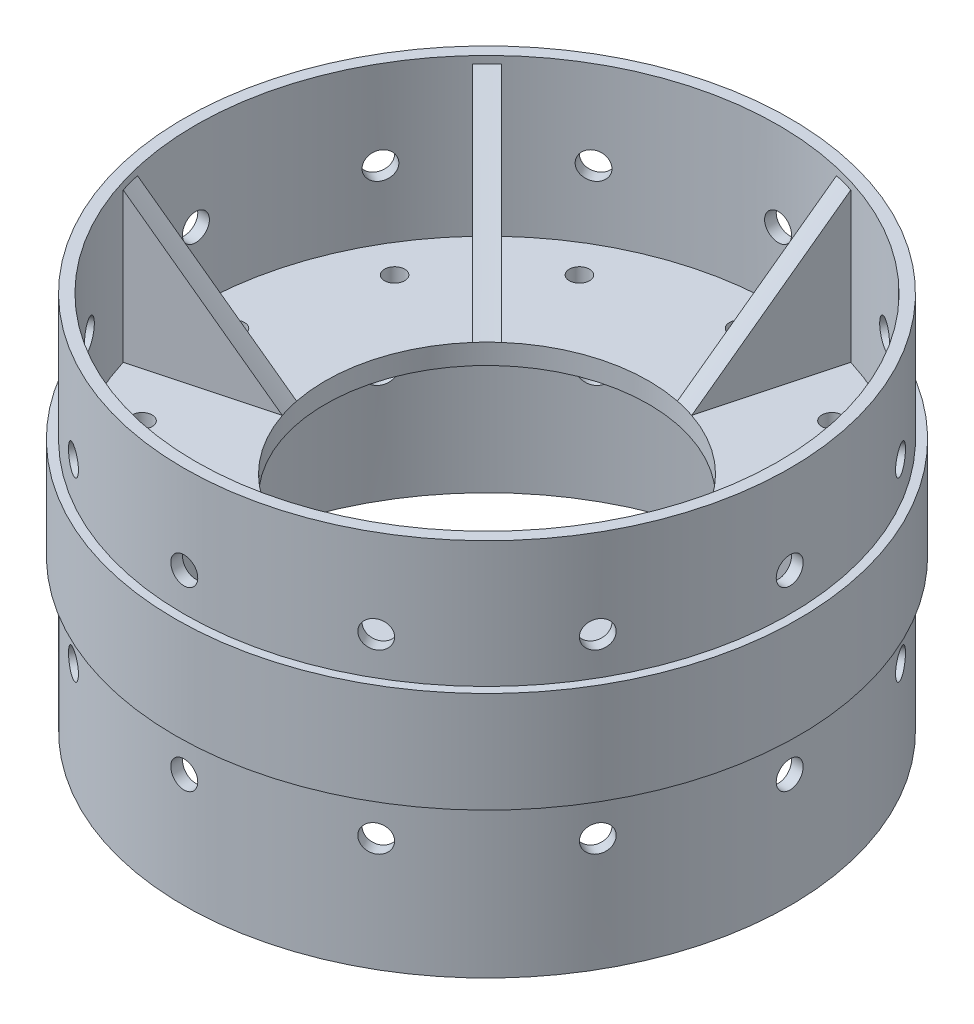
SolidWorks part; units mm, degrees
material "Onyx"
ref_plane "Front Plane" through (0, 0, 0) normal (0, 0, 1) x (1, 0, 0)
ref_plane "Top Plane" through (0, 0, 0) normal (0, 1, 0) x (1, 0, 0)
ref_plane "Right Plane" through (0, 0, 0) normal (1, 0, 0) x (0, 0, -1)
sketch "Sketch1" plane through (0, 0, 0) normal (0, 1, 0) x (1, 0, 0)
  circle A0 centre (0, 0) radius 73.279
  circle A1 centre (0, 0) radius 78.359
  dimension "D1" = 146.558
  dimension "D2" = 156.718
extrude "Boss-Extrude1" add sketch "Sketch1" along normal blind 25.4
sketch "Sketch2" plane through (0, 25.4, 0) normal (0, 1, 0) x (1, 0, 0)
  circle A0 centre (0, 0) radius 76.2
  circle A1 centre (0, 0) radius 73.279
  circle A2 centre (0, 0) radius 73.279 construction
  dimension "D1" = 0
extrude "Boss-Extrude2" add sketch "Sketch2" along normal blind 31.75
sketch "Sketch3" plane through (0, 0, 0) normal (0, -1, 0) x (1, 0, 0)
  circle A0 centre (0, 0) radius 76.2
  circle A1 centre (0, 0) radius 73.279
  circle A2 centre (0, 0) radius 73.279 construction
  dimension "D1" = 152.4
  dimension "D2" = 0
extrude "Boss-Extrude3" add sketch "Sketch3" along normal blind 38.1
ref_plane "Plane1" through (0, 12.7, 0) normal (0, 1, 0) x (1, 0, 0)
sketch "Sketch4" plane through (0, 12.7, 0) normal (0, 1, 0) x (1, 0, 0)
  circle A0 centre (0, 0) radius 74.549
  circle A1 centre (0, 0) radius 40.64
  dimension "D1" = 81.28
extrude "Boss-Extrude4" add sketch "Sketch4" along normal blind 5.08
sketch "Sketch5" plane through (0, 17.78, 0) normal (0, 1, 0) x (1, 0, 0)
  line L3 (0, 0) -> (40.64, 0) construction
  line L35 (38.5211, 12.9513) -> (70.0821, 21.4081)
  line L36 (39.8359, 8.0444) -> (71.3969, 16.5012)
  line L37 (70.7821, 18.966) -> (0, 0) construction
  line L38 (26.8846, -30.4767) -> (49.9889, -53.581)
  line L39 (30.4767, -26.8846) -> (53.581, -49.9889)
  line L40 (-12.9513, -38.5211) -> (-21.4081, -70.0821)
  line L41 (-8.0444, -39.8359) -> (-16.5012, -71.3969)
  line L42 (-39.8359, -8.0444) -> (-71.3969, -16.5012)
  line L43 (-38.5211, -12.9513) -> (-70.0821, -21.4081)
  line L44 (-26.8846, 30.4767) -> (-49.9889, 53.581)
  line L45 (-30.4767, 26.8846) -> (-53.581, 49.9889)
  line L46 (12.9513, 38.5211) -> (21.4081, 70.0821)
  line L47 (8.0444, 39.8359) -> (16.5012, 71.3969)
  circle A0 centre (0, 0) radius 40.64 construction
  circle A3 centre (0, 0) radius 73.279 construction
  arc A34 (70.0821, 21.4081) -> (71.3969, 16.5012) centre (0, 0) cw
  arc A35 (38.5211, 12.9513) -> (39.8359, 8.0444) centre (0, 0) cw
  arc A36 (30.4767, -26.8846) -> (26.8846, -30.4767) centre (0, 0) cw
  arc A37 (53.581, -49.9889) -> (49.9889, -53.581) centre (0, 0) cw
  arc A38 (-8.0444, -39.8359) -> (-12.9513, -38.5211) centre (0, 0) cw
  arc A39 (-16.5012, -71.3969) -> (-21.4081, -70.0821) centre (0, 0) cw
  arc A40 (-38.5211, -12.9513) -> (-39.8359, -8.0444) centre (0, 0) cw
  arc A41 (-70.0821, -21.4081) -> (-71.3969, -16.5012) centre (0, 0) cw
  arc A42 (-30.4767, 26.8846) -> (-26.8846, 30.4767) centre (0, 0) cw
  arc A43 (-53.581, 49.9889) -> (-49.9889, 53.581) centre (0, 0) cw
  arc A44 (8.0444, 39.8359) -> (12.9513, 38.5211) centre (0, 0) cw
  arc A45 (16.5012, 71.3969) -> (21.4081, 70.0821) centre (0, 0) cw
  point P29 (0, 0)
  point P34 (0, 0)
  point P40 (0, 0)
  point P42 (39.2552, 10.5184)
  dimension "D1" = 15
  dimension "D2" = 6
  dimension "D5" = 5.08
extrude "Boss-Extrude10" add sketch "Sketch5" along normal blind 38.862
chamfer "Chamfer1" distance 38.862 distance2 33.782 6 edges at (-39.2552, 56.642, 10.5184) (-10.5184, 56.642, 39.2552) (28.7368, 56.642, 28.7368) (39.2552, 56.642, -10.5184) (10.5184, 56.642, -39.2552) (-28.7368, 56.642, -28.7368) first distance on face at (0, 37.211, 0)
sketch "Sketch7" plane through (0, 0, 0) normal (0, 0, 1) x (1, 0, 0)
  line L0 (0, 42.3302) -> (0, 74.728) construction
  line L1 (78.359, 25.4) -> (-78.359, 25.4) construction
  line L2 (-78.359, 12.7) -> (83.2334, 12.7) construction
  line L3 (-78.359, 25.4) -> (-78.359, 0) construction
  circle A0 centre (0, 34.925) radius 3.3909
  circle A1 centre (0, -9.525) radius 3.3909
  dimension "D1" = 6.7818
  dimension "D2" = 9.525
extrude "Cut-Extrude2" cut sketch "Sketch7" against normal through all
ref_axis "Axis1" through (0, 42.3302, 0) along (0, 1, 0)
pattern_circular "CirPattern2" count 12 over 360 about axis through (0, 42.3302, 0) along (0, 1, 0) of "Cut-Extrude2"
sketch "Sketch8" plane through (0, 17.78, 0) normal (0, 1, 0) x (1, 0, 0)
  circle A0 centre (0, 63.5) radius 2.54
  circle A1 centre (31.75, 54.9926) radius 2.54
  circle A2 centre (54.9926, 31.75) radius 2.54
  circle A3 centre (63.5, 0) radius 2.54
  circle A4 centre (54.9926, -31.75) radius 2.54
  circle A5 centre (31.75, -54.9926) radius 2.54
  circle A6 centre (0, -63.5) radius 2.54
  circle A7 centre (-31.75, -54.9926) radius 2.54
  circle A8 centre (-54.9926, -31.75) radius 2.54
  circle A9 centre (-63.5, 0) radius 2.54
  circle A10 centre (-54.9926, 31.75) radius 2.54
  circle A11 centre (-31.75, 54.9926) radius 2.54
  point P27 (0, 0)
  dimension "D1" = 5.08
  dimension "D2" = 63.5
  dimension "D3" = 0
  dimension "D4" = 12
extrude "Cut-Extrude3" cut sketch "Sketch8" against normal up to next
